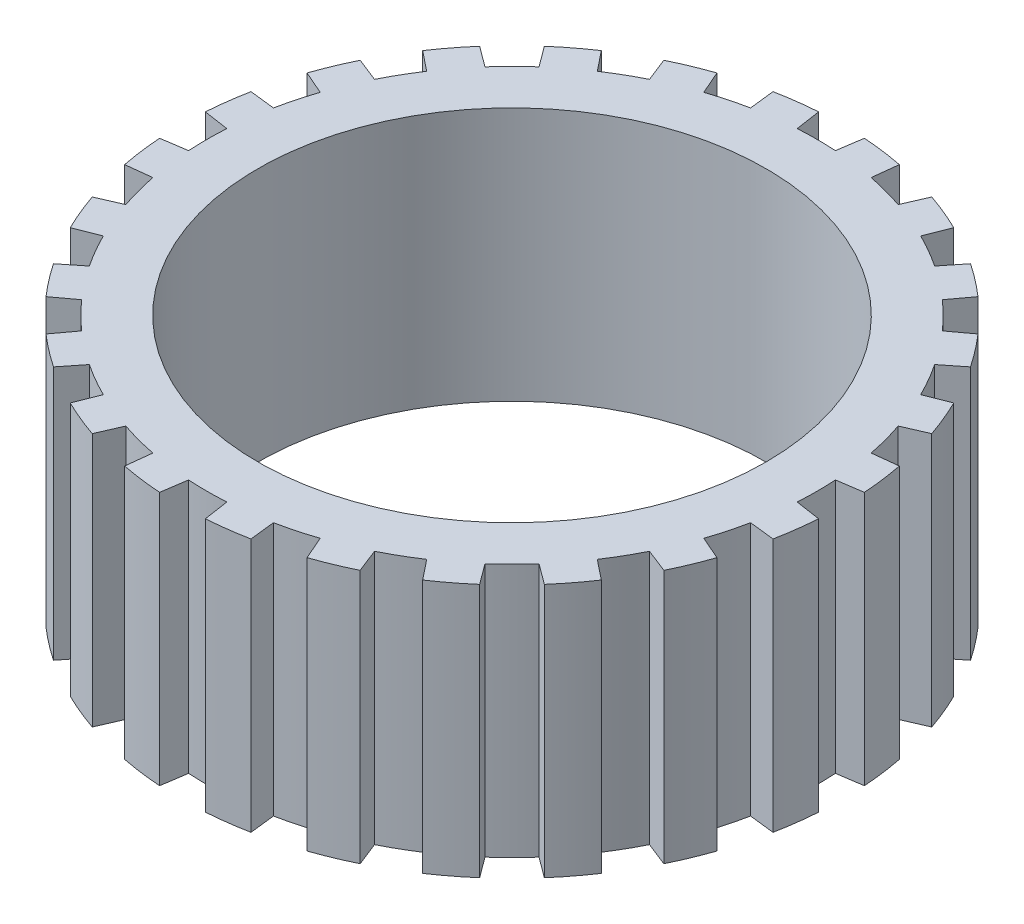
SolidWorks part; units mm, degrees
ref_plane "Front Plane" through (0, 0, 0) normal (0, 0, 1) x (1, 0, 0)
ref_plane "Top Plane" through (0, 0, 0) normal (0, 1, 0) x (1, 0, 0)
ref_plane "Right Plane" through (0, 0, 0) normal (1, 0, 0) x (0, 0, -1)
sketch "Sketch2" plane through (0, 0, 0) normal (0, 0, 1) x (1, 0, 0)
  line L0 (50, 0) -> (60, 0)
  line L2 (28.875, 0) -> (-28.875, 0) construction
  line L3 (60, 0) -> (60, 50)
  line L4 (60, 50) -> (50, 50)
  line L5 (50, 50) -> (50, 0)
  line L7 (0, -1000) -> (0, 49000) construction
  point P12 (0, 0)
  dimension "D1" = 10
  dimension "D2" = 100
  dimension "D3" = 50
revolve "Revolve1" add sketch "Sketch2" angle 360 about L7
sketch "Sketch3" plane through (0, 0, 0) normal (0, 1, 0) x (1, 0, 0)
  line L0 (0, -1000) -> (0, 49000) construction
  line L1 (4.5023, 64.8439) -> (3.7608, 59.882)
  line L2 (11.866, 58.815) -> (12.4339, 63.7997)
  line L3 (8.3093, 84.3659) -> (-4892.5477, -49674.8704) construction
  line L4 (8.4842, 64.4439) -> (7.8316, 59.4867) construction
  line L5 (21.1318, 61.4691) -> (19.1312, 56.8682)
  line L6 (26.6841, 53.7397) -> (28.5228, 58.4076)
  line L7 (36.3211, 53.9053) -> (33.1979, 49.979)
  line L8 (39.6837, 45.0023) -> (42.6679, 49.0352)
  line L9 (49.0352, 42.6679) -> (45.0023, 39.6837)
  line L10 (49.979, 33.1979) -> (53.9053, 36.3211)
  line L11 (58.4076, 28.5228) -> (53.7397, 26.6841)
  line L12 (4.5023, 64.8439) -> (0, 60) construction
  line L13 (56.8682, 19.1312) -> (61.4691, 21.1318)
  line L14 (63.7997, 12.4339) -> (58.815, 11.866)
  line L15 (59.882, 3.7608) -> (64.8439, 4.5023)
  line L16 (60, 0) -> (64.8439, 4.5023) construction
  line L17 (64.8439, -4.5023) -> (59.882, -3.7608)
  line L18 (58.815, -11.866) -> (63.7997, -12.4339)
  line L19 (61.4691, -21.1318) -> (56.8682, -19.1312)
  line L20 (53.7397, -26.6841) -> (58.4076, -28.5228)
  line L21 (53.9053, -36.3211) -> (49.979, -33.1979)
  line L22 (45.0023, -39.6837) -> (49.0352, -42.6679)
  line L23 (42.6679, -49.0352) -> (39.6837, -45.0023)
  line L24 (33.1979, -49.979) -> (36.3211, -53.9053)
  line L25 (28.5228, -58.4076) -> (26.6841, -53.7397)
  line L26 (19.1312, -56.8682) -> (21.1318, -61.4691)
  line L27 (12.4339, -63.7997) -> (11.866, -58.815)
  line L28 (3.7608, -59.882) -> (4.5023, -64.8439)
  line L29 (-4.5023, -64.8439) -> (-3.7608, -59.882)
  line L30 (-11.866, -58.815) -> (-12.4339, -63.7997)
  line L31 (-21.1318, -61.4691) -> (-19.1312, -56.8682)
  line L32 (-26.6841, -53.7397) -> (-28.5228, -58.4076)
  line L33 (-36.3211, -53.9053) -> (-33.1979, -49.979)
  line L34 (-39.6837, -45.0023) -> (-42.6679, -49.0352)
  line L35 (-49.0352, -42.6679) -> (-45.0023, -39.6837)
  line L36 (-49.979, -33.1979) -> (-53.9053, -36.3211)
  line L37 (-58.4076, -28.5228) -> (-53.7397, -26.6841)
  line L38 (-56.8682, -19.1312) -> (-61.4691, -21.1318)
  line L39 (-63.7997, -12.4339) -> (-58.815, -11.866)
  line L40 (-59.882, -3.7608) -> (-64.8439, -4.5023)
  line L41 (-64.8439, 4.5023) -> (-59.882, 3.7608)
  line L42 (-58.815, 11.866) -> (-63.7997, 12.4339)
  line L43 (-61.4691, 21.1318) -> (-56.8682, 19.1312)
  line L44 (-53.7397, 26.6841) -> (-58.4076, 28.5228)
  line L45 (-53.9053, 36.3211) -> (-49.979, 33.1979)
  line L46 (-45.0023, 39.6837) -> (-49.0352, 42.6679)
  line L47 (-42.6679, 49.0352) -> (-39.6837, 45.0023)
  line L48 (-33.1979, 49.979) -> (-36.3211, 53.9053)
  line L49 (-28.5228, 58.4076) -> (-26.6841, 53.7397)
  line L50 (-19.1312, 56.8682) -> (-21.1318, 61.4691)
  line L51 (-12.4339, 63.7997) -> (-11.866, 58.815)
  line L52 (-3.7608, 59.882) -> (-4.5023, 64.8439)
  line L53 (-4.5023, 64.8439) -> (4.5023, 64.8439) construction
  line L54 (12.4339, 63.7997) -> (21.1318, 61.4691) construction
  line L55 (0, 60) -> (-4.5023, 64.8439) construction
  circle A0 centre (0, 0) radius 60 construction
  arc A1 (4.5023, 64.8439) -> (12.4339, 63.7997) centre (0, 0) cw
  arc A2 (3.7608, 59.882) -> (11.866, 58.815) centre (0, 0) cw
  arc A3 (19.1312, 56.8682) -> (26.6841, 53.7397) centre (0, 0) cw
  arc A4 (21.1318, 61.4691) -> (28.5228, 58.4076) centre (0, 0) cw
  arc A5 (33.1979, 49.979) -> (39.6837, 45.0023) centre (0, 0) cw
  arc A6 (36.3211, 53.9053) -> (42.6679, 49.0352) centre (0, 0) cw
  arc A7 (45.0023, 39.6837) -> (49.979, 33.1979) centre (0, 0) cw
  arc A8 (49.0352, 42.6679) -> (53.9053, 36.3211) centre (0, 0) cw
  arc A9 (53.7397, 26.6841) -> (56.8682, 19.1312) centre (0, 0) cw
  arc A10 (58.4076, 28.5228) -> (61.4691, 21.1318) centre (0, 0) cw
  arc A11 (58.815, 11.866) -> (59.882, 3.7608) centre (0, 0) cw
  arc A12 (63.7997, 12.4339) -> (64.8439, 4.5023) centre (0, 0) cw
  arc A13 (59.882, -3.7608) -> (58.815, -11.866) centre (0, 0) cw
  arc A14 (64.8439, -4.5023) -> (63.7997, -12.4339) centre (0, 0) cw
  arc A15 (56.8682, -19.1312) -> (53.7397, -26.6841) centre (0, 0) cw
  arc A16 (61.4691, -21.1318) -> (58.4076, -28.5228) centre (0, 0) cw
  arc A17 (49.979, -33.1979) -> (45.0023, -39.6837) centre (0, 0) cw
  arc A18 (53.9053, -36.3211) -> (49.0352, -42.6679) centre (0, 0) cw
  arc A19 (39.6837, -45.0023) -> (33.1979, -49.979) centre (0, 0) cw
  arc A20 (42.6679, -49.0352) -> (36.3211, -53.9053) centre (0, 0) cw
  arc A21 (26.6841, -53.7397) -> (19.1312, -56.8682) centre (0, 0) cw
  arc A22 (28.5228, -58.4076) -> (21.1318, -61.4691) centre (0, 0) cw
  arc A23 (11.866, -58.815) -> (3.7608, -59.882) centre (0, 0) cw
  arc A24 (12.4339, -63.7997) -> (4.5023, -64.8439) centre (0, 0) cw
  arc A25 (-3.7608, -59.882) -> (-11.866, -58.815) centre (0, 0) cw
  arc A26 (-4.5023, -64.8439) -> (-12.4339, -63.7997) centre (0, 0) cw
  arc A27 (-19.1312, -56.8682) -> (-26.6841, -53.7397) centre (0, 0) cw
  arc A28 (-21.1318, -61.4691) -> (-28.5228, -58.4076) centre (0, 0) cw
  arc A29 (-33.1979, -49.979) -> (-39.6837, -45.0023) centre (0, 0) cw
  arc A30 (-36.3211, -53.9053) -> (-42.6679, -49.0352) centre (0, 0) cw
  arc A31 (-45.0023, -39.6837) -> (-49.979, -33.1979) centre (0, 0) cw
  arc A32 (-49.0352, -42.6679) -> (-53.9053, -36.3211) centre (0, 0) cw
  arc A33 (-53.7397, -26.6841) -> (-56.8682, -19.1312) centre (0, 0) cw
  arc A34 (-58.4076, -28.5228) -> (-61.4691, -21.1318) centre (0, 0) cw
  arc A35 (-58.815, -11.866) -> (-59.882, -3.7608) centre (0, 0) cw
  arc A36 (-63.7997, -12.4339) -> (-64.8439, -4.5023) centre (0, 0) cw
  arc A37 (-59.882, 3.7608) -> (-58.815, 11.866) centre (0, 0) cw
  arc A38 (-64.8439, 4.5023) -> (-63.7997, 12.4339) centre (0, 0) cw
  arc A39 (-56.8682, 19.1312) -> (-53.7397, 26.6841) centre (0, 0) cw
  arc A40 (-61.4691, 21.1318) -> (-58.4076, 28.5228) centre (0, 0) cw
  arc A41 (-49.979, 33.1979) -> (-45.0023, 39.6837) centre (0, 0) cw
  arc A42 (-53.9053, 36.3211) -> (-49.0352, 42.6679) centre (0, 0) cw
  arc A43 (-39.6837, 45.0023) -> (-33.1979, 49.979) centre (0, 0) cw
  arc A44 (-42.6679, 49.0352) -> (-36.3211, 53.9053) centre (0, 0) cw
  arc A45 (-26.6841, 53.7397) -> (-19.1312, 56.8682) centre (0, 0) cw
  arc A46 (-28.5228, 58.4076) -> (-21.1318, 61.4691) centre (0, 0) cw
  arc A47 (-11.866, 58.815) -> (-3.7608, 59.882) centre (0, 0) cw
  arc A48 (-12.4339, 63.7997) -> (-4.5023, 64.8439) centre (0, 0) cw
  point P28 (0, 0)
  point P111 (0, 0)
  dimension "D1" = 120
  dimension "D2" = 5
  dimension "D4" = 5.625
  dimension "D5" = 6
  dimension "D6" = 8
  dimension "D3" = 2
  dimension "D8" = 4
extrude "Boss-Extrude1" add sketch "Sketch3" along normal blind 50
